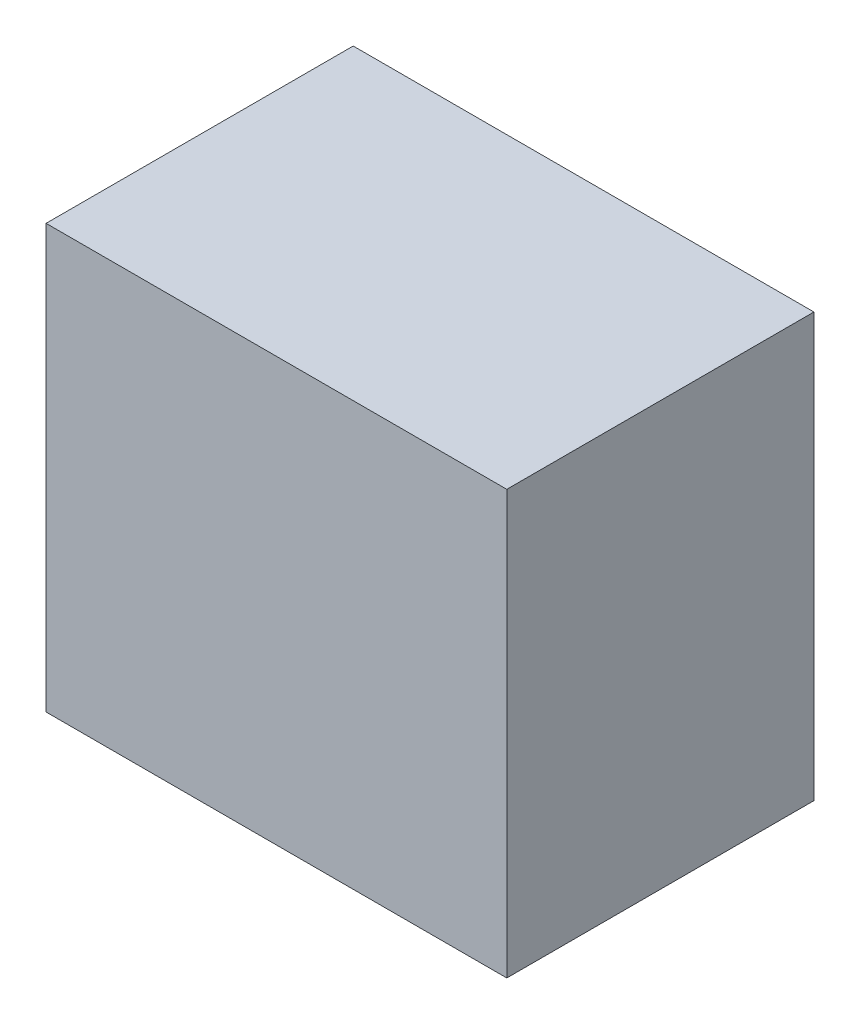
SolidWorks part; units mm, degrees
ref_plane "Front Plane" through (0, 0, 0) normal (0, 0, 1) x (1, 0, 0)
ref_plane "Top Plane" through (0, 0, 0) normal (0, 1, 0) x (1, 0, 0)
ref_plane "Right Plane" through (0, 0, 0) normal (1, 0, 0) x (0, 0, -1)
sketch "Sketch1" plane through (0, 0, 0) normal (0, 1, 0) x (1, 0, 0)
  line L1 (0, 0) -> (76.2, 0)
  line L2 (0, 0) -> (0, 50.8)
  line L3 (0, 50.8) -> (76.2, 50.8)
  line L4 (76.2, 0) -> (76.2, 50.8)
  dimension "D1" = 76.2
  dimension "D2" = 50.8
extrude "Boss-Extrude1" add sketch "Sketch1" along normal blind 70
